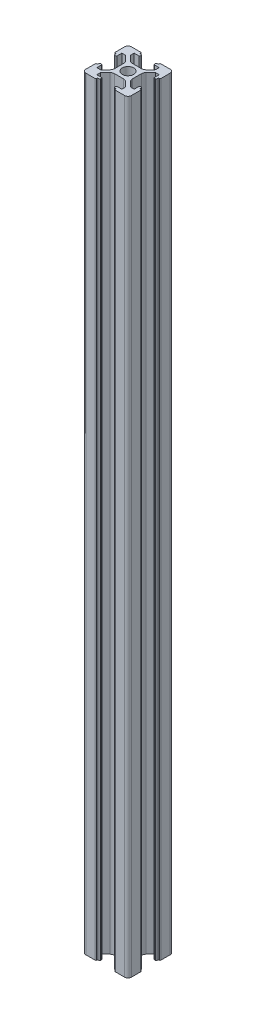
SolidWorks part; units mm, degrees
ref_plane "Front Plane" through (0, 0, 0) normal (0, 0, 1) x (1, 0, 0)
ref_plane "Top Plane" through (0, 0, 0) normal (0, 1, 0) x (1, 0, 0)
ref_plane "Right Plane" through (0, 0, 0) normal (1, 0, 0) x (0, 0, -1)
sketch "Sketch1" plane through (0, 0, 0) normal (0, 1, 0) x (1, 0, 0)
  line L0 (3.4251, 4.4858) -> (5.5, 6.5607)
  line L1 (-10, -10) -> (10, -10) construction
  line L2 (-10, -10) -> (-10, 10) construction
  line L3 (-10, 10) -> (10, 10) construction
  line L4 (10, -10) -> (10, 10) construction
  line L5 (-10, -10) -> (10, 10) construction
  line L6 (-10, 10) -> (10, -10) construction
  line L9 (0, 3.9) -> (2.0109, 3.9)
  line L10 (3.9, 0) -> (3.9, 2.0109)
  line L11 (3.9, 0) -> (3.9, -2.0109)
  line L12 (4.4858, -3.4251) -> (6.5607, -5.5)
  line L13 (4.4858, 3.4251) -> (6.5607, 5.5)
  line L14 (5.5, 8.2) -> (3.1, 8.2)
  line L15 (3.1, 8.2) -> (3.1, 9.24)
  line L16 (5.5, 8.2) -> (5.5, 6.5607)
  line L17 (8.2, 5.5) -> (6.5607, 5.5)
  line L21 (4.1, 10) -> (4.1, 9.24)
  line L22 (8.2, 5.5) -> (8.2, 3.1)
  line L23 (8.2, 3.1) -> (9.24, 3.1)
  line L24 (9.24, 3.1) -> (9.24, 4.1)
  line L25 (10, 4.1) -> (9.24, 4.1)
  line L26 (0, 0) -> (50000, 0) construction
  line L27 (0, 0) -> (0, -50000) construction
  line L28 (4.1, 10) -> (8.5, 10)
  line L29 (10, 8.5) -> (10, 4.1)
  line L30 (4.1, 9.24) -> (3.1, 9.24)
  line L31 (8.2, -5.5) -> (6.5607, -5.5)
  line L32 (8.2, -5.5) -> (8.2, -3.1)
  line L33 (8.2, -3.1) -> (9.24, -3.1)
  line L34 (9.24, -4.1) -> (9.24, -3.1)
  line L35 (10, -4.1) -> (9.24, -4.1)
  line L36 (10, -4.1) -> (10, -8.5)
  line L37 (8.5, -10) -> (4.1, -10)
  line L38 (4.1, -10) -> (4.1, -9.24)
  line L39 (3.1, -9.24) -> (4.1, -9.24)
  line L40 (3.1, -8.2) -> (3.1, -9.24)
  line L41 (5.5, -8.2) -> (3.1, -8.2)
  line L42 (5.5, -8.2) -> (5.5, -6.5607)
  line L43 (3.4251, -4.4858) -> (5.5, -6.5607)
  line L44 (0, -3.9) -> (2.0109, -3.9)
  line L45 (0, -3.9) -> (-2.0109, -3.9)
  line L46 (-3.4251, -4.4858) -> (-5.5, -6.5607)
  line L47 (-5.5, -8.2) -> (-5.5, -6.5607)
  line L48 (-5.5, -8.2) -> (-3.1, -8.2)
  line L49 (-3.1, -8.2) -> (-3.1, -9.24)
  line L50 (-4.1, -9.24) -> (-3.1, -9.24)
  line L51 (-4.1, -10) -> (-4.1, -9.24)
  line L52 (-4.1, -10) -> (-8.5, -10)
  line L53 (-10, -8.5) -> (-10, -4.1)
  line L54 (-10, -4.1) -> (-9.24, -4.1)
  line L55 (-9.24, -3.1) -> (-9.24, -4.1)
  line L56 (-8.2, -3.1) -> (-9.24, -3.1)
  line L57 (-8.2, -5.5) -> (-8.2, -3.1)
  line L58 (-8.2, -5.5) -> (-6.5607, -5.5)
  line L59 (-4.4858, -3.4251) -> (-6.5607, -5.5)
  line L60 (-3.9, 0) -> (-3.9, -2.0109)
  line L61 (-3.9, 0) -> (-3.9, 2.0109)
  line L62 (-4.4858, 3.4251) -> (-6.5607, 5.5)
  line L63 (-8.2, 5.5) -> (-6.5607, 5.5)
  line L64 (-8.2, 5.5) -> (-8.2, 3.1)
  line L65 (-8.2, 3.1) -> (-9.24, 3.1)
  line L66 (-9.24, 4.1) -> (-9.24, 3.1)
  line L67 (-10, 4.1) -> (-9.24, 4.1)
  line L68 (-10, 4.1) -> (-10, 8.5)
  line L69 (-8.5, 10) -> (-4.1, 10)
  line L70 (-4.1, 10) -> (-4.1, 9.24)
  line L71 (-3.1, 9.24) -> (-4.1, 9.24)
  line L72 (-3.1, 8.2) -> (-3.1, 9.24)
  line L73 (-5.5, 8.2) -> (-3.1, 8.2)
  line L74 (-5.5, 8.2) -> (-5.5, 6.5607)
  line L75 (-3.4251, 4.4858) -> (-5.5, 6.5607)
  line L76 (0, 3.9) -> (-2.0109, 3.9)
  arc A1 (3.9, 2.0109) -> (4.4858, 3.4251) centre (5.9, 2.0109) cw
  arc A2 (3.4251, 4.4858) -> (2.0109, 3.9) centre (2.0109, 5.9) cw
  arc A3 (10, 8.5) -> (8.5, 10) centre (8.5, 8.5) ccw
  arc A4 (2.5, 0) -> (0, 2.5) centre (0, 0) ccw
  arc A5 (0, -2.5) -> (2.5, 0) centre (0, 0) ccw
  arc A6 (4.4858, -3.4251) -> (3.9, -2.0109) centre (5.9, -2.0109) cw
  arc A7 (8.5, -10) -> (10, -8.5) centre (8.5, -8.5) ccw
  arc A8 (2.0109, -3.9) -> (3.4251, -4.4858) centre (2.0109, -5.9) cw
  arc A9 (-2.5, 0) -> (0, -2.5) centre (0, 0) ccw
  arc A10 (-3.4251, -4.4858) -> (-2.0109, -3.9) centre (-2.0109, -5.9) cw
  arc A11 (-10, -8.5) -> (-8.5, -10) centre (-8.5, -8.5) ccw
  arc A12 (-3.9, -2.0109) -> (-4.4858, -3.4251) centre (-5.9, -2.0109) cw
  arc A13 (0, 2.5) -> (-2.5, 0) centre (0, 0) ccw
  arc A14 (-4.4858, 3.4251) -> (-3.9, 2.0109) centre (-5.9, 2.0109) cw
  arc A15 (-8.5, 10) -> (-10, 8.5) centre (-8.5, 8.5) ccw
  arc A16 (-2.0109, 3.9) -> (-3.4251, 4.4858) centre (-2.0109, 5.9) cw
  point P0 (0, 0)
  point P30 (3.1, 10)
  point P115 (0, 0)
  dimension "D2" = 2.5
  dimension "D3" = 2
  dimension "D12" = 1.5
  dimension "D1" = 20
  dimension "D4" = 1.5
  dimension "D5" = 1.8
  dimension "D6" = 5.5
  dimension "D7" = 0.76
  dimension "D8" = 3.1
  dimension "D9" = 1
  dimension "D10" = 3.9
  dimension "D11" = 3.9
  dimension "D13" = 4
extrude "Boss-Extrude1" add sketch "Sketch1" along normal blind 335 contours L76 A16 L75 L74 L73 L72 L71 L70 L69 A15 L68 L67 L66 L65 L64 L63 L62 A14 L61 L60 A12 L59 L58 L57 L56 L55 L54 L53 A11 L52 L51 L50 L49 L48 L47 L46 A10 L45 L44 A8 L43 L42 L41 L40 L39 L38 L37 A7 L36 L35 L34 region at (4.6626, 0, -5.3232)
fillet "Fillet1" radius 0.35 33 edges at (-4.1, 167.5, -10) (-4.1, 167.5, -9.24) (-3.1, 167.5, -9.24) (-3.1, 167.5, -8.2) (-9.24, 167.5, -4.1) (-10, 167.5, -4.1) (-9.24, 167.5, -3.1) (-8.2, 167.5, -3.1) (-10, 167.5, 4.1) (-9.24, 167.5, 4.1) (-9.24, 167.5, 3.1) (-8.2, 167.5, 3.1) (-4.1, 167.5, 10) (-4.1, 167.5, 9.24) (-3.1, 167.5, 9.24) (-3.1, 167.5, 8.2) (4.1, 167.5, 10) (4.1, 167.5, 9.24) (3.1, 167.5, 9.24) (3.1, 167.5, 8.2) (10, 167.5, 4.1) (9.24, 167.5, 4.1) (9.24, 167.5, 3.1) (8.2, 167.5, 3.1) (10, 167.5, -4.1) (9.24, 167.5, -4.1) (9.24, 167.5, -3.1) (8.2, 167.5, -3.1) (3.1, 167.5, -8.2) (4.1, 167.5, -10) (5.5, 167.5, -6.5607) (3.1, 167.5, -9.24) (4.1, 167.5, -9.24)
